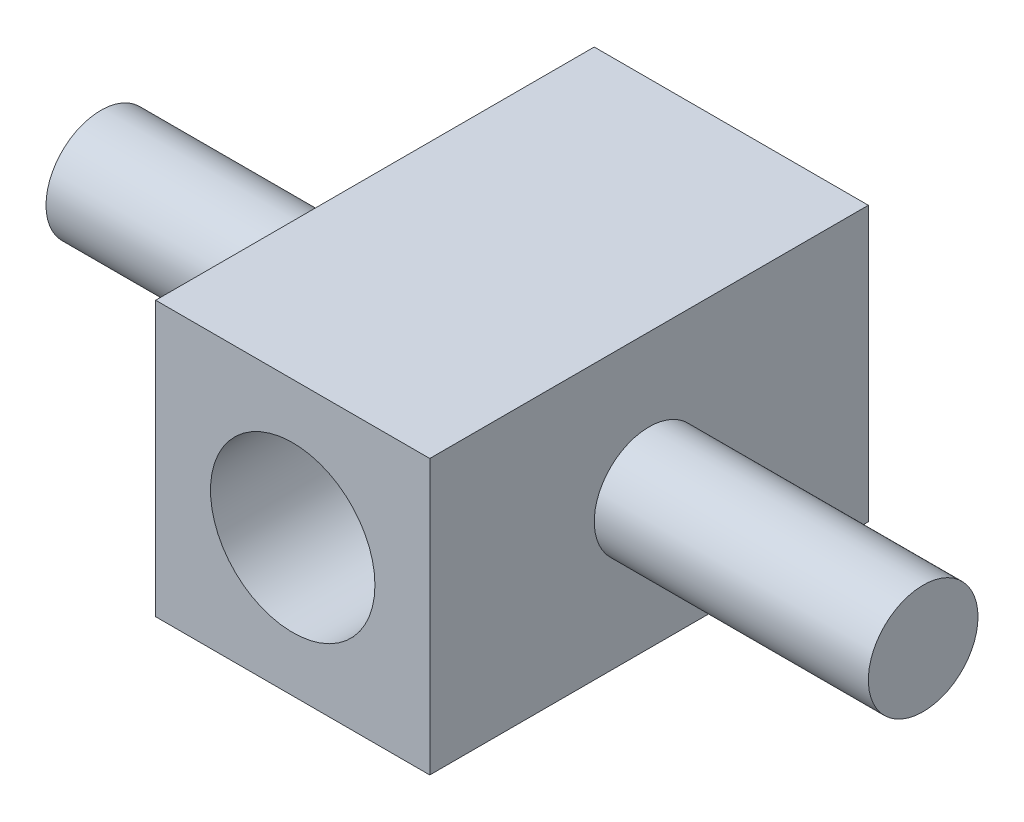
SolidWorks part; units mm, degrees
ref_plane "Front Plane" through (0, 0, 0) normal (0, 0, 1) x (1, 0, 0)
ref_plane "Top Plane" through (0, 0, 0) normal (0, 1, 0) x (1, 0, 0)
ref_plane "Right Plane" through (0, 0, 0) normal (1, 0, 0) x (0, 0, -1)
sketch "Sketch1" plane through (0, 0, 0) normal (0, 0, 1) x (1, 0, 0)
  line L1 (-3.175, -3.175) -> (3.175, -3.175)
  line L2 (-3.175, -3.175) -> (-3.175, 3.175)
  line L3 (-3.175, 3.175) -> (3.175, 3.175)
  line L4 (3.175, -3.175) -> (3.175, 3.175)
  circle A1 centre (0, 0) radius 1.905
  dimension "D1" = 3.81
  dimension "D2" = 3.175
  dimension "D3" = 3.175
  dimension "D4" = 3.175
  dimension "D5" = 3.175
extrude "Boss-Extrude1" add sketch "Sketch1" along normal blind 5.08 and the other way blind 5.08
sketch "Sketch2" plane through (-3.175, 0, 0) normal (-1, 0, 0) x (0, 0, 1)
  circle A0 centre (0, 0) radius 1.27
  dimension "D1" = 2.54
extrude "Boss-Extrude2" add sketch "Sketch2" along normal blind 6.35
sketch "Sketch3" plane through (3.175, 0, 0) normal (1, 0, 0) x (0, 0, -1)
  circle A0 centre (0, 0) radius 1.27
  dimension "D1" = 2.54
extrude "Boss-Extrude3" add sketch "Sketch3" along normal blind 6.35
scale "Scale1" scale about centroid uniform scaling yes scale factor 8
